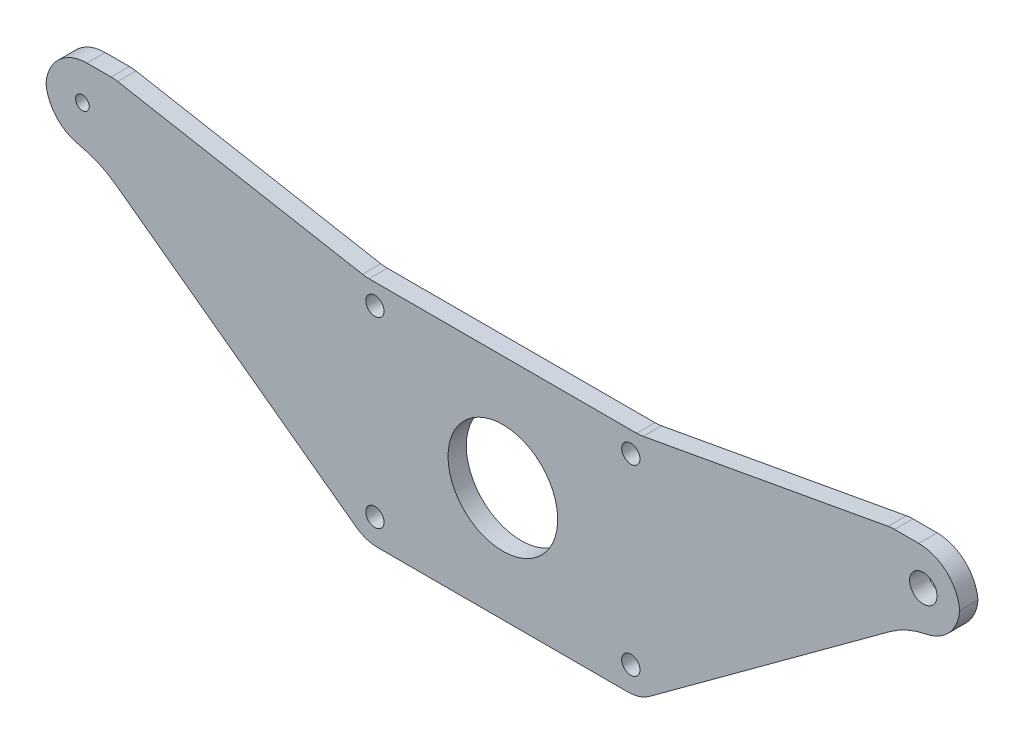
SolidWorks part; units mm, degrees
ref_plane "Front" through (0, 0, 0) normal (0, 0, 1) x (1, 0, 0)
ref_plane "Top" through (0, 0, 0) normal (0, 1, 0) x (1, 0, 0)
ref_plane "Right" through (0, 0, 0) normal (1, 0, 0) x (0, 0, -1)
sketch "草图1" plane through (0, 0, 0) normal (0, 0, 1) x (1, 0, 0)
  line L0 (-100, 10) -> (-85, 10)
  line L1 (-85, 10) -> (-30, 0)
  line L2 (-30, 0) -> (30, 0)
  line L3 (30, 0) -> (85, 10)
  line L4 (85, 10) -> (100, 10)
  line L5 (100, 10) -> (100, -6)
  line L6 (100, -6) -> (90, -6)
  line L7 (90, -6) -> (30, -50)
  line L8 (-30, -50) -> (30, -50)
  line L11 (-30, -50) -> (-90, -6)
  line L12 (-90, -6) -> (-100, -6)
  line L13 (-100, -6) -> (-100, 10)
  point P2 (0, 0)
  point P9 (36.8765, 0)
  dimension "D1" = 16
  dimension "D2" = 60
  dimension "D3" = 15
  dimension "D4" = 10
  dimension "D5" = 10
  dimension "D6" = 60
  dimension "D7" = 200
  dimension "D8" = 60
extrude "凸台-拉伸1" add sketch "草图1" along normal blind 4
fillet "圆角1" radius 8 6 edges at (85, 10, 2) (30, 0, 2) (-85, 10, 2) (-30, 0, 2) (-30, -50, 2) (30, -50, 2)
fillet "圆角2" radius 20 2 edges at (-90, -6, 2) (90, -6, 2)
sketch "草图3" plane through (0, 0, 0) normal (0, 0, -1) x (-1, 0, 0)
  line L0 (-29.2786, 0) -> (29.2786, 0) construction
  circle A0 centre (-28, -4.5) radius 2
  circle A1 centre (-28, -44.5) radius 2
  point P4 (0, 0)
  point P5 (-27.9673, -3.0656)
  point P6 (-29.34, -1.6795)
  point P7 (-28.9433, -41.8181)
  point P8 (-27.9603, -1.0297)
  point P11 (-55.5438, 5.0058)
  point P14 (0, 0)
  dimension "D1" = 4
  dimension "D2" = 40
  dimension "D3" = 4.5
  dimension "D4" = 28
extrude "切除-拉伸2" cut sketch "草图3" against normal through all contours A0 | A1
sketch "草图2" plane through (0, 0, 0) normal (0, 0, -1) x (-1, 0, 0)
  circle A0 centre (0, -25) radius 12
  dimension "D1" = 24
  dimension "D2" = 25
extrude "切除-拉伸1" cut sketch "草图2" against normal through all
mirror "镜向1" about plane through (0, 0, 0) normal (1, 0, 0) of "切除-拉伸2"
sketch "草图4" plane through (0, 0, 0) normal (0, 0, -1) x (-1, 0, 0)
  line L0 (100, 10) -> (100, -6) construction
  circle A0 centre (92, 2) radius 1.5
  point P4 (0, 0)
  point P5 (100, 2)
  dimension "D1" = 3
  dimension "D2" = 8
extrude "切除-拉伸3" cut sketch "草图4" against normal through all
mirror "镜向2" about plane through (0, 0, 0) normal (1, 0, 0) of "切除-拉伸3"
fillet "圆角3" radius 9 4 edges at (100, -6, 2) (100, 10, 2) (-100, -6, 2) (-100, 10, 2)
sketch "草图5" plane through (0, 0, 0) normal (0, 0, -1) x (-1, 0, 0)
  circle A0 centre (-92, 2) radius 3
  circle A1 centre (-92, 2) radius 1.5 construction
  circle A2 centre (-92, 2) radius 1.5
  dimension "D1" = 6
extrude "切除-拉伸4" cut sketch "草图5" against normal blind 25
